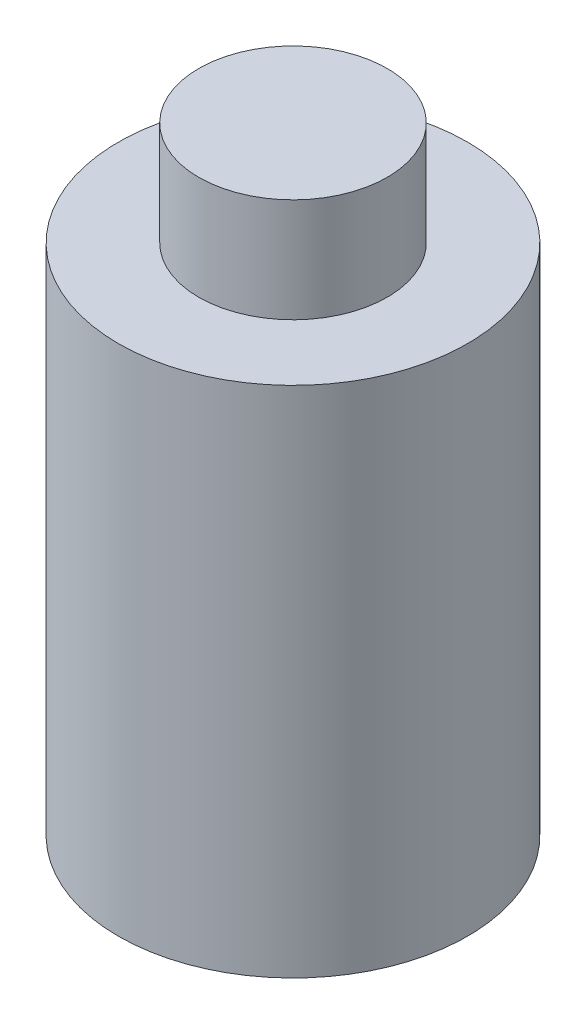
SolidWorks part; units mm, degrees
ref_plane "Front Plane" through (0, 0, 0) normal (0, 0, 1) x (1, 0, 0)
ref_plane "Top Plane" through (0, 0, 0) normal (0, 1, 0) x (1, 0, 0)
ref_plane "Right Plane" through (0, 0, 0) normal (1, 0, 0) x (0, 0, -1)
sketch "Sketch1" plane through (0, 0, 0) normal (0, 1, 0) x (1, 0, 0)
  circle A0 centre (0, 0) radius 2.7
  circle A1 centre (0, 0) radius 5
  dimension "D1" = 5.4
  dimension "D2" = 10
extrude "Boss-Extrude1" add sketch "Sketch1" along normal blind 14.7
extrude "Boss-Extrude2" add sketch "Sketch1<2>" along normal blind 17.675 contours A0 region at (0, 0, 0)
sketch "Sketch1<2>" plane through (0, 0, 0) normal (0, 1, 0) x (1, 0, 0) same geometry as "Sketch1"
